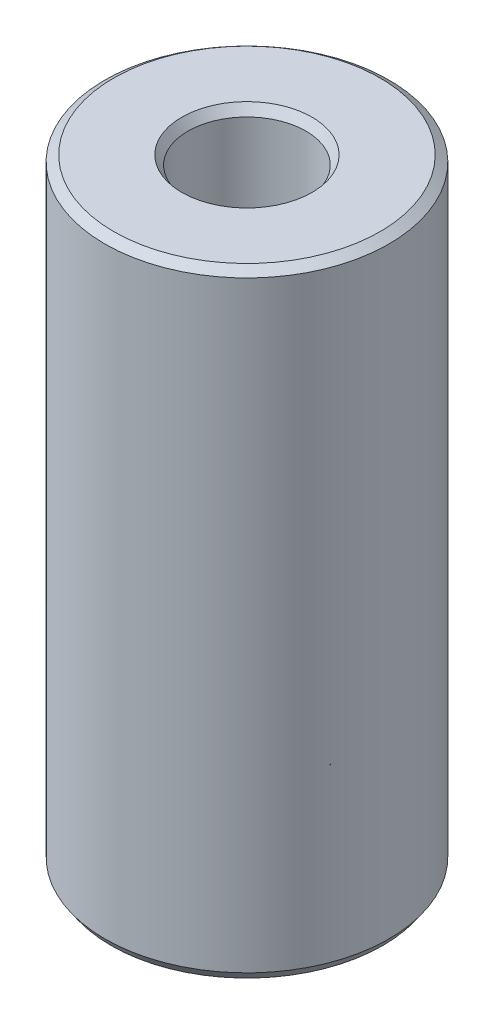
SolidWorks part; units mm, degrees
ref_plane "Front Plane" through (0, 0, 0) normal (0, 0, 1) x (1, 0, 0)
ref_plane "Top Plane" through (0, 0, 0) normal (0, 1, 0) x (1, 0, 0)
ref_plane "Right Plane" through (0, 0, 0) normal (1, 0, 0) x (0, 0, -1)
sketch "Sketch1" plane through (0, 0, 0) normal (0, 1, 0) x (1, 0, 0)
  circle A0 centre (0, 0) radius 32.5
  dimension "SLEEVE_OD" = 65
extrude "Boss-Extrude1" add sketch "Sketch1" along normal blind 141.1564
sketch "Sketch2" plane through (0, 0, 0) normal (0, 1, 0) x (1, 0, 0)
  circle A0 centre (0, 0) radius 13.4924
  dimension "BORE_D" = 26.9847
extrude "Cut-Extrude1" cut sketch "Sketch2" along normal through all
chamfer "Chamfer1" distance 1.4223 angle 55.122 4 edges at (0, 141.1564, 13.4924) (0, 0, 13.4924) (0, 0, 32.5) (0, 141.1564, 32.5) first distance on face at (0, 141.1564, 13.4924) first distance on face at (0, 0, 13.4924) first distance on face at (0, 141.1564, 32.5)
